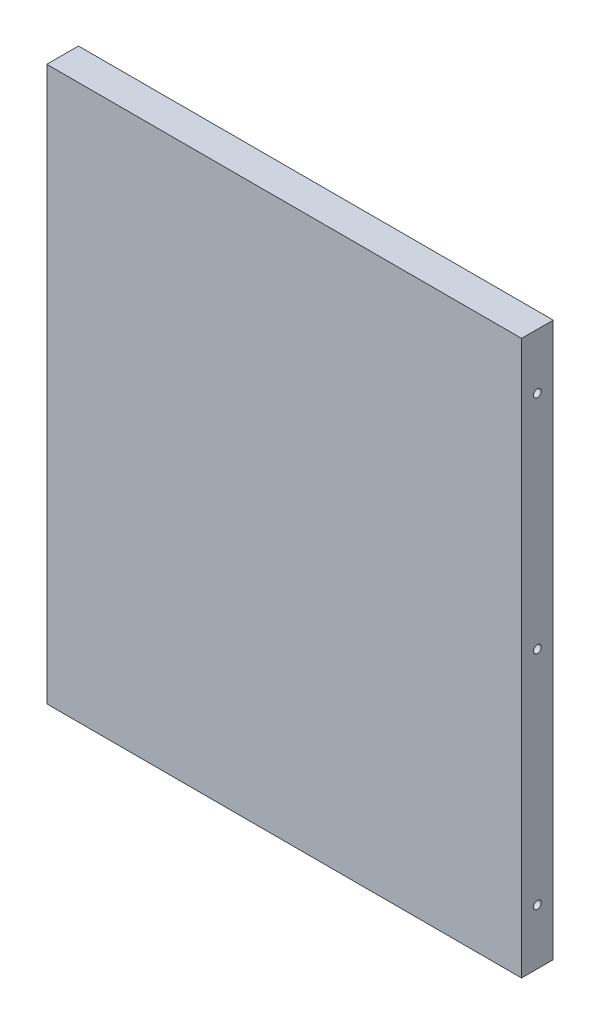
SolidWorks part; units mm, degrees
material "3.0205 (EN-AW 1200)"
ref_plane "Ebene vorne" through (0, 0, 0) normal (0, 0, 1) x (1, 0, 0)
ref_plane "Ebene oben" through (0, 0, 0) normal (0, 1, 0) x (1, 0, 0)
ref_plane "Ebene rechts" through (0, 0, 0) normal (1, 0, 0) x (0, 0, -1)
sketch "Skizze1" plane through (0, 0, 0) normal (0, 0, 1) x (1, 0, 0)
  line L1 (-84.7009, 65.5769) -> (65.2991, 65.5769)
  line L2 (-84.7009, 65.5769) -> (-84.7009, -109.4231)
  line L3 (-84.7009, -109.4231) -> (65.2991, -109.4231)
  line L4 (65.2991, 65.5769) -> (65.2991, -109.4231)
  dimension "D1" = 150
  dimension "D2" = 175
extrude "Aufsatz-Linear austragen1" add sketch "Skizze1" along normal blind 10
sketch "Skizze2" plane through (-84.7009, 0, 0) normal (-1, 0, 0) x (0, 0, 1)
  line L0 (0, -21.9231) -> (10, -21.9231) construction
  line L1 (0, 65.5769) -> (0, -109.4231) construction
  line L2 (10, 65.5769) -> (10, -109.4231) construction
  line L3 (5, -91.9231) -> (5, -21.9231) construction
  line L4 (5, -21.9231) -> (5, 48.0769) construction
  circle A0 centre (5, 48.0769) radius 1.25
  circle A1 centre (5, -21.9231) radius 1.25
  circle A3 centre (5, -91.9231) radius 1.23
  point P11 (5, -21.9231)
  dimension "D2" = 2.5
  dimension "D3" = 2.46
  dimension "D1" = 70
extrude "Schnitt-Linear austragen1" cut sketch "Skizze2" against normal blind 5
sketch "Skizze3" plane through (65.2991, 0, 0) normal (1, 0, 0) x (0, 0, -1)
  line L0 (-10, -21.9231) -> (0, -21.9231) construction
  line L1 (-5, -91.9231) -> (-5, -21.9231) construction
  line L2 (-5, -21.9231) -> (-5, 48.0769) construction
  line L4 (0, -109.4231) -> (0, 65.5769) construction
  line L5 (-10, -109.4231) -> (-10, 65.5769) construction
  circle A0 centre (-5, 48.0769) radius 1.23
  circle A1 centre (-5, -21.9231) radius 1.23
  circle A3 centre (-5, -91.9231) radius 1.23
  point P7 (-5, -21.9231)
  dimension "D2" = 2.46
  dimension "D3" = 2.46
  dimension "D1" = 70
extrude "Schnitt-Linear austragen2" cut sketch "Skizze3" against normal blind 5
